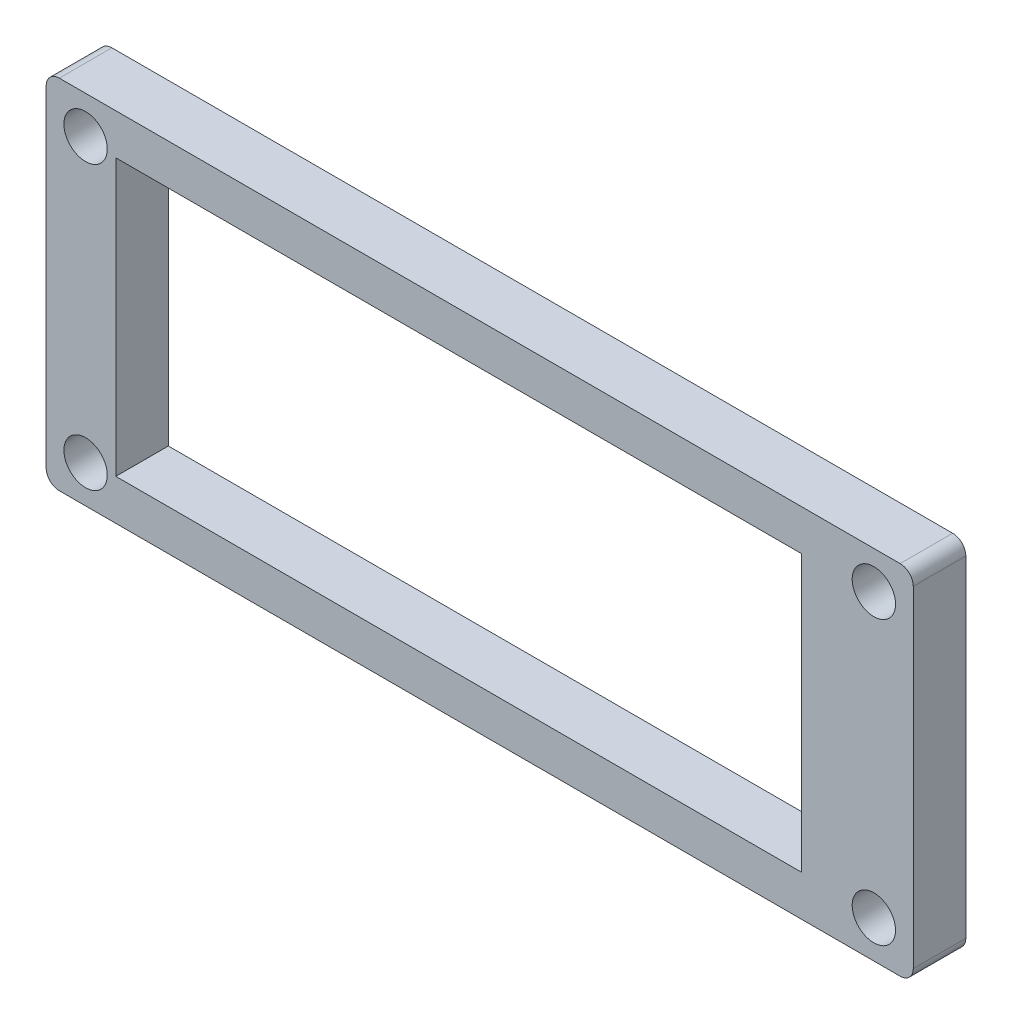
SolidWorks part; units mm, degrees
ref_plane "Front Plane" through (0, 0, 0) normal (0, 0, 1) x (1, 0, 0)
ref_plane "Top Plane" through (0, 0, 0) normal (0, 1, 0) x (1, 0, 0)
ref_plane "Right Plane" through (0, 0, 0) normal (1, 0, 0) x (0, 0, -1)
sketch "Sketch2" plane through (0, 0, 0) normal (0, 0, 1) x (1, 0, 0)
  line L0 (33.6, -13.6) -> (-30.4, -13.6) construction
  line L1 (-31.4, -12.6) -> (-31.4, 12.6) construction
  line L2 (-30.4, 13.6) -> (33.6, 13.6) construction
  line L3 (34.6, 12.6) -> (34.6, -12.6) construction
  line L4 (33.6, -13.6) -> (-30.4, -13.6)
  line L5 (-31.4, -12.6) -> (-31.4, 12.6)
  line L6 (-30.4, 13.6) -> (33.6, 13.6)
  line L7 (34.6, 12.6) -> (34.6, -12.6)
  line L10 (-25.1, 10.5) -> (25.1, 10.5)
  line L11 (-26.1, 10.5) -> (26.1, 10.5)
  line L12 (-26.1, -9.5) -> (-26.1, 9.5)
  line L13 (25.1, -10.5) -> (-25.1, -10.5)
  line L14 (26.1, -10.5) -> (-26.1, -10.5)
  line L15 (-26.1, -10.5) -> (-26.1, 10.5)
  line L16 (-27.03, -5.69) -> (-29.77, -5.69) construction
  line L17 (26.1, 9.5) -> (26.1, -9.5)
  line L18 (26.1, 10.5) -> (26.1, -10.5)
  line L19 (-27.03, 4.67) -> (-27.03, -5.69) construction
  line L20 (-29.77, 4.67) -> (-27.03, 4.67) construction
  line L21 (-29.77, -5.69) -> (-29.77, 4.67) construction
  line L22 (29.77, -5.69) -> (27.03, -5.69) construction
  line L23 (27.03, -5.69) -> (27.03, 4.67) construction
  line L24 (27.03, 4.67) -> (29.77, 4.67) construction
  line L25 (29.77, 4.67) -> (29.77, -5.69) construction
  line L26 (-27.03, -5.69) -> (-29.77, -5.69)
  line L27 (-27.03, 4.67) -> (-27.03, -5.69)
  line L28 (-29.77, 4.67) -> (-27.03, 4.67)
  line L29 (-29.77, -5.69) -> (-29.77, 4.67)
  line L30 (29.77, -5.69) -> (27.03, -5.69)
  line L31 (27.03, -5.69) -> (27.03, 4.67)
  line L32 (27.03, 4.67) -> (29.77, 4.67)
  line L33 (29.77, 4.67) -> (29.77, -5.69)
  arc A0 (33.6, -13.6) -> (34.6, -12.6) centre (33.6, -12.6) ccw construction
  arc A1 (-31.4, -12.6) -> (-30.4, -13.6) centre (-30.4, -12.6) ccw construction
  arc A2 (-30.4, 13.6) -> (-31.4, 12.6) centre (-30.4, 12.6) ccw construction
  arc A3 (34.6, 12.6) -> (33.6, 13.6) centre (33.6, 12.6) ccw construction
  arc A4 (33.6, -13.6) -> (34.6, -12.6) centre (33.6, -12.6) ccw
  arc A5 (-31.4, -12.6) -> (-30.4, -13.6) centre (-30.4, -12.6) ccw
  arc A6 (-30.4, 13.6) -> (-31.4, 12.6) centre (-30.4, 12.6) ccw
  arc A7 (34.6, 12.6) -> (33.6, 13.6) centre (33.6, 12.6) ccw
  arc A8 (30.152, 11.5411) -> (33.048, 9.9589) centre (31.6, 10.75) ccw construction
  arc A9 (33.048, 9.9589) -> (30.152, 11.5411) centre (31.6, 10.75) ccw construction
  arc A10 (30.152, -9.9589) -> (33.048, -11.5411) centre (31.6, -10.75) ccw construction
  arc A11 (33.048, -11.5411) -> (30.152, -9.9589) centre (31.6, -10.75) ccw construction
  arc A12 (-29.848, -9.9589) -> (-26.952, -11.5411) centre (-28.4, -10.75) ccw construction
  arc A13 (-26.952, -11.5411) -> (-29.848, -9.9589) centre (-28.4, -10.75) ccw construction
  arc A14 (-29.848, 11.5411) -> (-26.952, 9.9589) centre (-28.4, 10.75) ccw construction
  arc A15 (-26.952, 9.9589) -> (-29.848, 11.5411) centre (-28.4, 10.75) ccw construction
  arc A16 (30.152, 11.5411) -> (33.048, 9.9589) centre (31.6, 10.75) ccw
  arc A17 (33.048, 9.9589) -> (30.152, 11.5411) centre (31.6, 10.75) ccw
  arc A18 (30.152, -9.9589) -> (33.048, -11.5411) centre (31.6, -10.75) ccw
  arc A19 (33.048, -11.5411) -> (30.152, -9.9589) centre (31.6, -10.75) ccw
  arc A20 (-29.848, -9.9589) -> (-26.952, -11.5411) centre (-28.4, -10.75) ccw
  arc A21 (-26.952, -11.5411) -> (-29.848, -9.9589) centre (-28.4, -10.75) ccw
  arc A22 (-29.848, 11.5411) -> (-26.952, 9.9589) centre (-28.4, 10.75) ccw
  arc A23 (-26.952, 9.9589) -> (-29.848, 11.5411) centre (-28.4, 10.75) ccw
  point P24 (26.1, 10.5)
  point P26 (26.1, 10.4666)
  point P31 (-26.1, 10.5)
  point P34 (26.1, 10.5)
  point P35 (-26.1, -10.5)
  point P36 (26.1, -10.5)
  point P38 (26.1, -10.5402)
  point P41 (-26.131, -10.5)
  point P44 (-26.1, 10.4609)
  dimension "D1" = 1
  dimension "D2" = 1
  dimension "D3" = 1
  dimension "D4" = 1
extrude "Boss-Extrude1" add sketch "Sketch2" along normal offset from surface (4 mm away) 4 contours L7 A7 L6 A6 L5 A5 L4 A4 A23 A22 A21 A20 A19 A18 A17 A16 L11 L18 L14 L15 | L29 L26 L27 L28 | L33 L32 L31 L30 region at (1.6, -12.8861, 0) region at (-28.4, -0.51, 0) region at (28.4, -0.51, 0)
extrude "Cut-Extrude1" cut sketch "Sketch2<3>" along normal blind 3 contours L29 L26 L27 L28 | L33 L30 L31 L32 region at (-28.4, -0.51, 0)
sketch "Sketch2<3>" plane through (0, 0, 0) normal (0, 0, 1) x (1, 0, 0) same geometry as "Sketch2"
